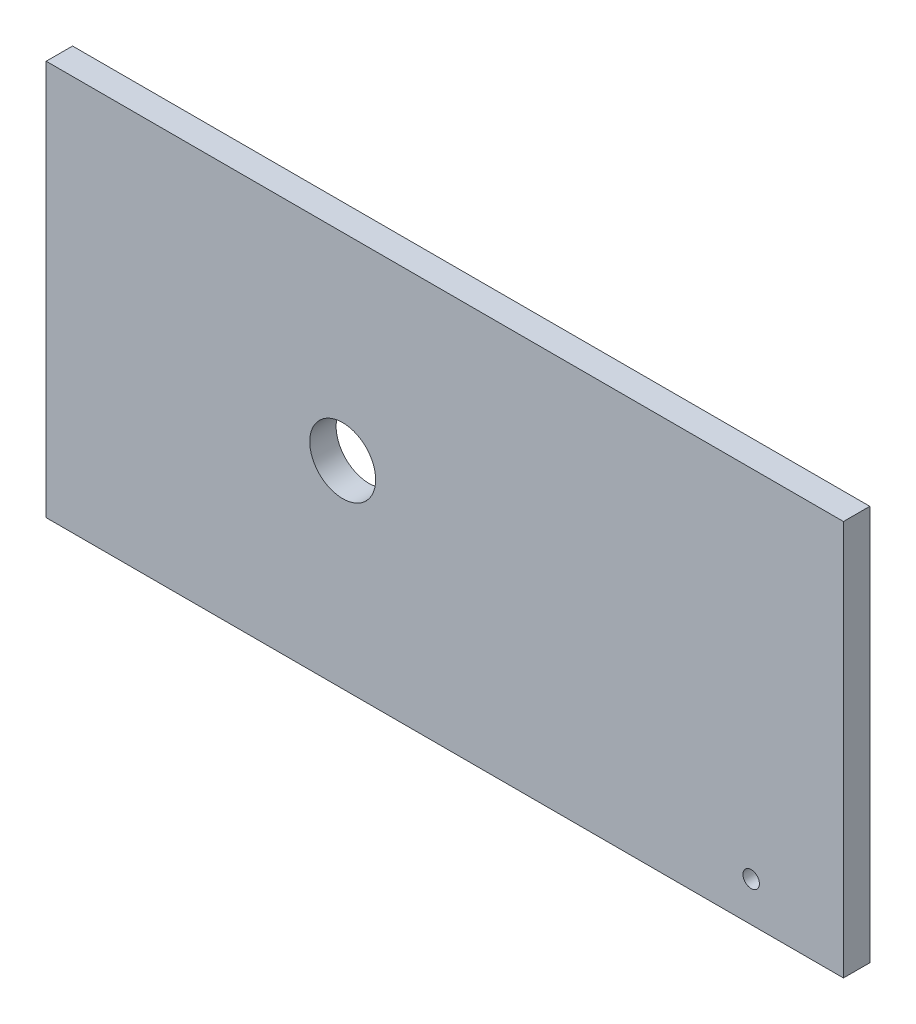
SolidWorks part; units mm, degrees
ref_plane "Front Plane" through (0, 0, 0) normal (0, 0, 1) x (1, 0, 0)
ref_plane "Top Plane" through (0, 0, 0) normal (0, 1, 0) x (1, 0, 0)
ref_plane "Right Plane" through (0, 0, 0) normal (1, 0, 0) x (0, 0, -1)
sketch "Sketch1" plane through (0, 0, 0) normal (0, 0, 1) x (1, 0, 0)
  line L1 (-81, -30) -> (40, -30)
  line L2 (-81, -30) -> (-81, 30)
  line L3 (-81, 30) -> (40, 30)
  line L11 (40, 30) -> (40, -30)
  circle A3 centre (-36, 0) radius 5
  circle A4 centre (26, -24) radius 1.25
  point P9 (-81, 0)
  dimension "D3" = 121
  dimension "D4" = 2.5
  dimension "D5" = 6
  dimension "D6" = 10
  dimension "D7" = 107
  dimension "D8" = 76
  dimension "D2" = 60
  dimension "D10" = 0
  dimension "D11" = 45
extrude "Boss-Extrude1" add sketch "Sketch1" along normal blind 4
